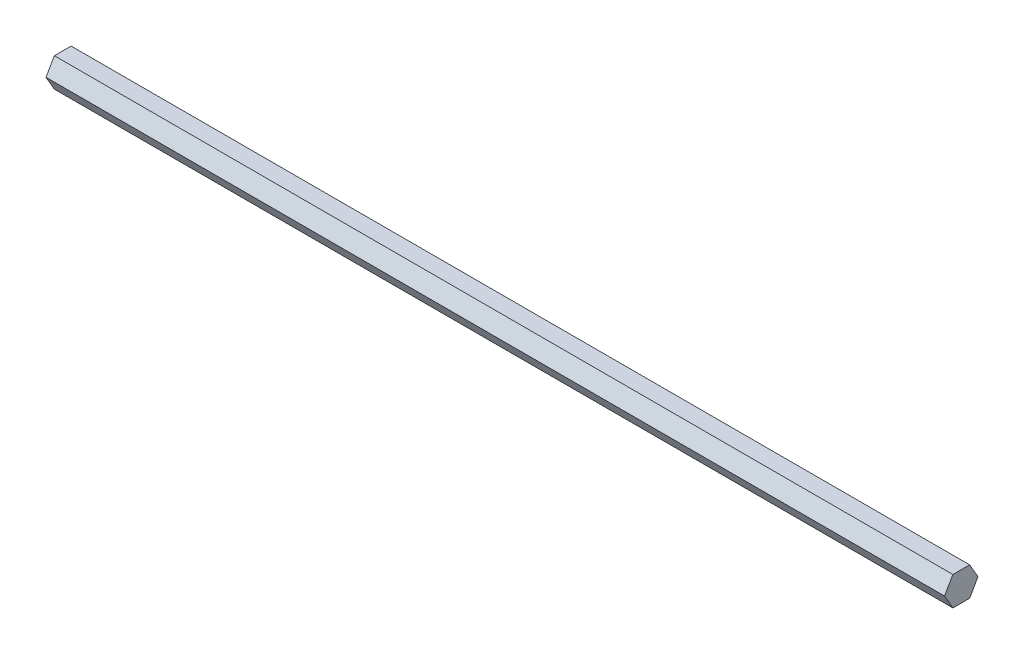
SolidWorks part; units mm, degrees
material "7075-T6 (SN)"
ref_plane "Front Plane" through (0, 0, 0) normal (0, 0, 1) x (1, 0, 0)
ref_plane "Top Plane" through (0, 0, 0) normal (0, 1, 0) x (1, 0, 0)
ref_plane "Right Plane" through (0, 0, 0) normal (1, 0, 0) x (0, 0, -1)
sketch "Sketch1" plane through (0, 0, 0) normal (1, 0, 0) x (0, 0, -1)
  line L1 (7.3323, 0) -> (3.6662, 6.35)
  line L2 (3.6662, 6.35) -> (-3.6662, 6.35)
  line L3 (-3.6662, 6.35) -> (-7.3323, 0)
  line L4 (-7.3323, 0) -> (-3.6662, -6.35)
  line L5 (-3.6662, -6.35) -> (3.6662, -6.35)
  line L6 (3.6662, -6.35) -> (7.3323, 0)
  circle A0 centre (0, 0) radius 6.35 construction
  dimension "D1" = 12.7
extrude "Boss-Extrude1" add sketch "Sketch1" along normal mid plane 393.7
ref_axis "Axis1" through (-230.505, 0, 0) along (1, 0, 0)
